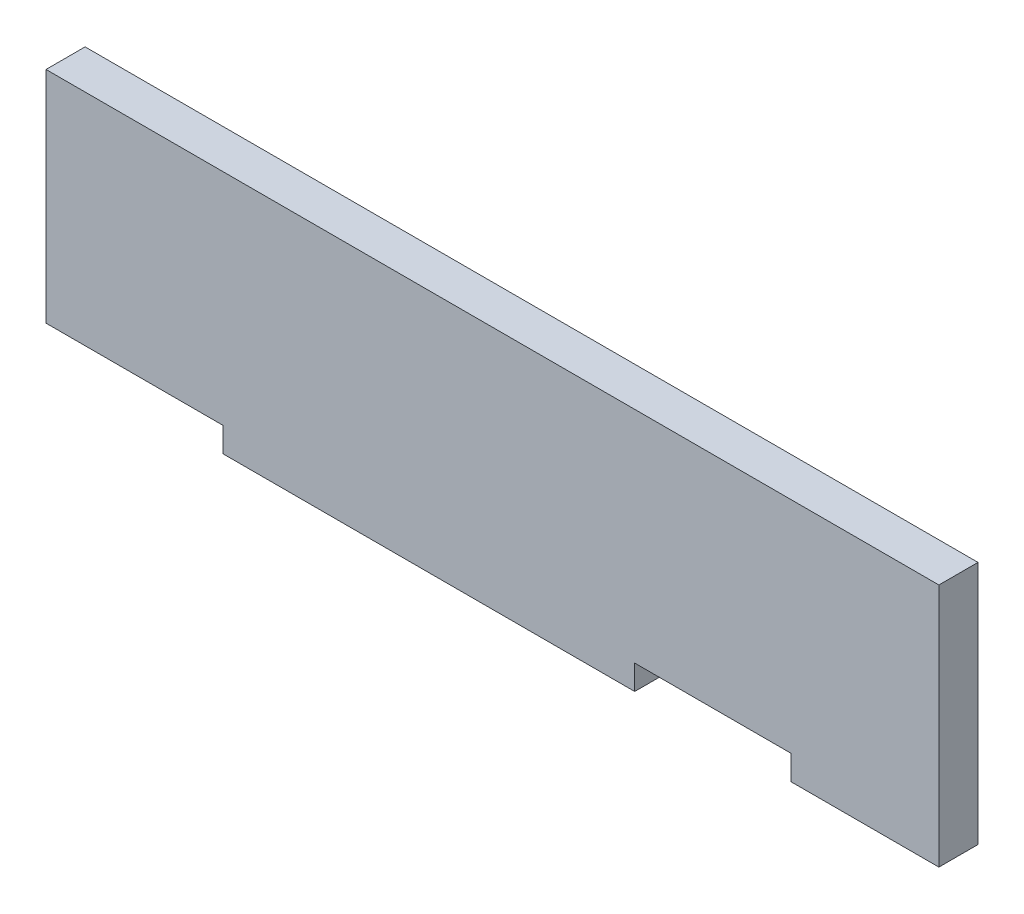
SolidWorks part; units mm, degrees
ref_plane "Front Plane" through (0, 0, 0) normal (0, 0, 1) x (1, 0, 0)
ref_plane "Top Plane" through (0, 0, 0) normal (0, 1, 0) x (1, 0, 0)
ref_plane "Right Plane" through (0, 0, 0) normal (1, 0, 0) x (0, 0, -1)
sketch "Sketch1" plane through (0, 0, 0) normal (0, 0, 1) x (1, 0, 0)
  line L1 (300, 0) -> (-135, 0)
  line L2 (300, 0) -> (300, 119.05)
  line L3 (300, 119.05) -> (-135, 119.05)
  line L4 (-135, 0) -> (-135, 119.05)
  line L5 (-135, 119.05) -> (300, 119.05) construction
  dimension "D1" = 119.05
  dimension "D2" = 435
extrude "Boss-Extrude1" add sketch "Sketch1" along normal blind 19.05
sketch "Sketch2" plane through (0, 0, 19.05) normal (0, 0, 1) x (1, 0, 0)
  line L1 (-48.8, 12) -> (-125, 12) construction
  line L2 (-48.8, 0) -> (-48.8, 12) construction
  line L3 (-135, 0) -> (300, 0) construction
  line L4 (151.8, 0) -> (151.8, 12) construction
  line L5 (151.8, 12) -> (228, 12) construction
  line L6 (228, 12) -> (228, 0) construction
  line L8 (-48.8, 12) -> (-125, 12)
  line L9 (-48.8, 0) -> (-48.8, 12)
  line L10 (-125, 0) -> (-48.8, 0)
  line L11 (151.8, 0) -> (151.8, 12)
  line L12 (151.8, 12) -> (228, 12)
  line L13 (228, 12) -> (228, 0)
  line L14 (151.8, 0) -> (228, 0)
  line L15 (-125, 12) -> (-135, 12)
  line L16 (-135, 119.05) -> (-135, 0) construction
  line L17 (-135, 12) -> (-135, 0)
  line L18 (-135, 0) -> (-125, 0)
extrude "Cut-Extrude1" cut sketch "Sketch2" against normal through all
